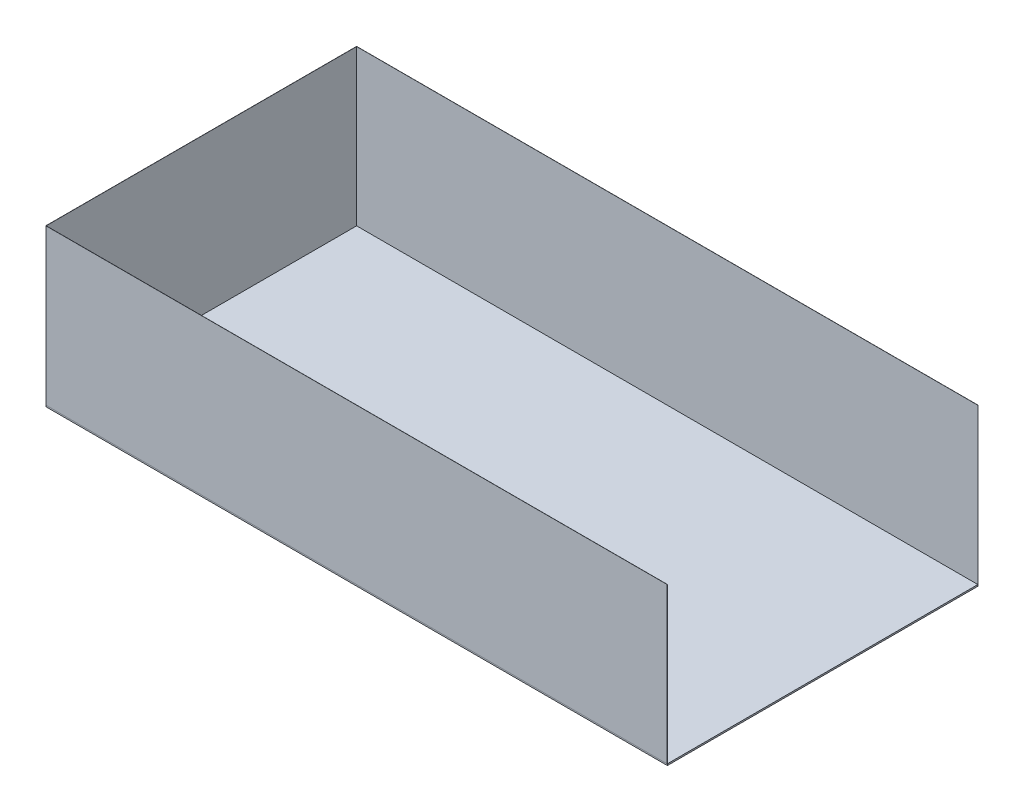
SolidWorks part; units mm, degrees
ref_plane "Front Plane" through (0, 0, 0) normal (0, 0, 1) x (1, 0, 0)
ref_plane "Top Plane" through (0, 0, 0) normal (0, 1, 0) x (1, 0, 0)
ref_plane "Right Plane" through (0, 0, 0) normal (1, 0, 0) x (0, 0, -1)
sketch "Sketch2" plane through (0, 0, 0) normal (0, 1, 0) x (1, 0, 0)
  line L1 (-39.5926, 33.6223) -> (62.0074, 33.6223)
  line L2 (-39.5926, 33.6223) -> (-39.5926, -17.1777)
  line L3 (-39.5926, -17.1777) -> (62.0074, -17.1777)
  line L4 (62.0074, 33.6223) -> (62.0074, -17.1777)
  dimension "Length_Floor" = 101.6
  dimension "Width_Floor" = 50.8
extrude "Floor" add sketch "Sketch2" along normal blind 0.254 contours L2 L1 L4 L3
sketch "Sketch4" plane through (0, 0.254, 0) normal (0, 1, 0) x (1, 0, 0)
  line L0 (-39.5926, 33.6223) -> (62.0074, 33.6223) construction
  line L1 (-39.5926, 33.6223) -> (62.0074, 33.6223)
extrude "Wall1" add sketch "Sketch4" along normal blind 25.4 thin thin type one direction wall 0.0254
sketch "Sketch5" plane through (0, 0.254, 0) normal (0, 1, 0) x (1, 0, 0)
  line L0 (-39.5926, 33.5969) -> (-39.5926, -17.1777) construction
  line L1 (-39.5926, 33.5969) -> (-39.5926, -17.1777)
extrude "Wall2" add sketch "Sketch5" along normal blind 25.4 separate body thin thin type one direction wall 0.0254
sketch "Sketch6" plane through (0, 0.254, 0) normal (0, 1, 0) x (1, 0, 0)
  line L0 (-39.5926, -17.1777) -> (62.0074, -17.1777) construction
  line L1 (-39.5926, -17.1777) -> (62.0074, -17.1777)
extrude "Wall3" add sketch "Sketch6" along normal blind 25.4 separate body thin thin type one direction wall 0.0254
